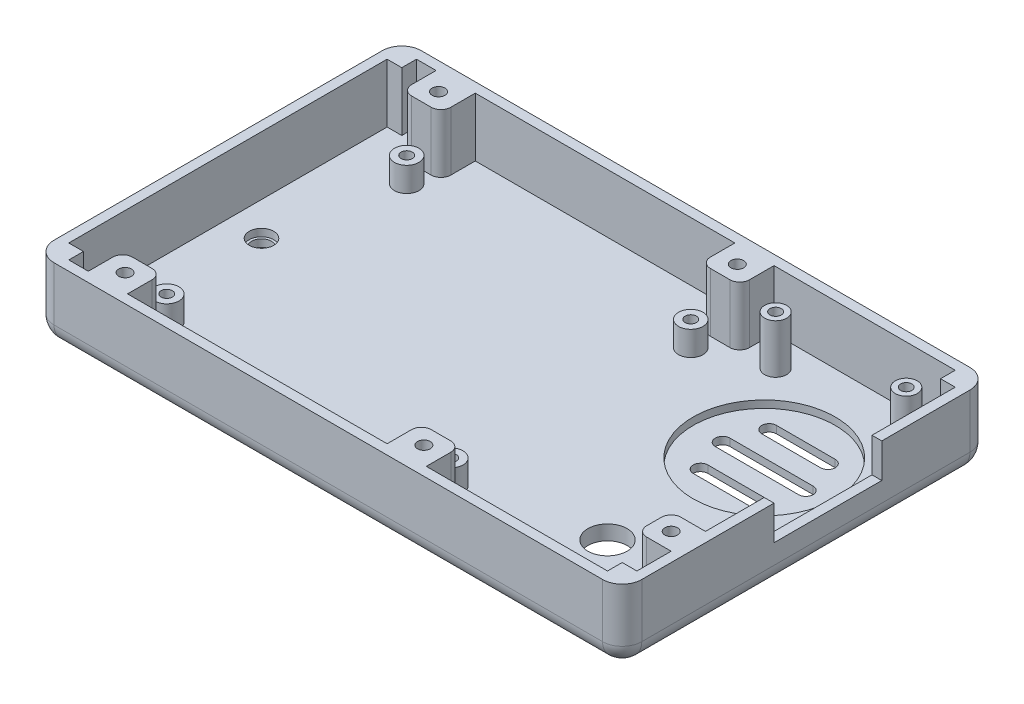
SolidWorks part; units mm, degrees
ref_plane "Front Plane" through (0, 0, 0) normal (0, 0, 1) x (1, 0, 0)
ref_plane "Top Plane" through (0, 0, 0) normal (0, 1, 0) x (1, 0, 0)
ref_plane "Right Plane" through (0, 0, 0) normal (1, 0, 0) x (0, 0, -1)
sketch "Sketch1" plane through (0, 0, 0) normal (0, 1, 0) x (1, 0, 0)
  line L1 (-60, 37.5) -> (60, 37.5)
  line L2 (-60, 37.5) -> (-60, -37.5)
  line L3 (-60, -37.5) -> (60, -37.5)
  line L4 (60, 37.5) -> (60, -37.5)
  line L5 (-60, 37.5) -> (60, -37.5) construction
  line L6 (-60, -37.5) -> (60, 37.5) construction
  point P0 (0, 0)
  dimension "D1" = 120
  dimension "D2" = 75
extrude "Main Structure" add sketch "Sketch1" along normal blind 15
sketch "Sketch2" plane through (0, 15, 0) normal (0, 1, 0) x (1, 0, 0)
  line L1 (-58, -35.5) -> (58, -35.5)
  line L2 (-58, -35.5) -> (-58, 35.5)
  line L3 (-58, 35.5) -> (58, 35.5)
  line L4 (58, -35.5) -> (58, 35.5)
  line L5 (-58, -35.5) -> (58, 35.5) construction
  line L6 (-58, 35.5) -> (58, -35.5) construction
  point P0 (0, 0)
  dimension "D1" = 71
  dimension "D2" = 116
extrude "Inside Cut" cut sketch "Sketch2" against normal blind 12
sketch "Sketch3" plane through (0, 3, 0) normal (0, 1, 0) x (1, 0, 0)
  line L0 (-58, 35.5) -> (-58, -35.5) construction
  line L1 (-58, -35.5) -> (58, -35.5) construction
  line L2 (58, 35.5) -> (-58, 35.5) construction
  circle A0 centre (-46, -24.5) radius 2.5
  circle A1 centre (-46, 24.5) radius 2.5
  circle A2 centre (-46, 24.5) radius 1.15
  circle A3 centre (-46, -24.5) radius 1.15
  circle A4 centre (12, 24.5) radius 2.5
  circle A5 centre (12, -24.5) radius 2.5
  circle A6 centre (12, 24.5) radius 1.15
  circle A7 centre (12, -24.5) radius 1.15
  dimension "D1" = 5
  dimension "D3" = 5
  dimension "D7" = 2.3
  dimension "D8" = 2.3
  dimension "D9" = 5
  dimension "D10" = 5
  dimension "D15" = 2.3
  dimension "D16" = 2.3
  dimension "D2" = 12
  dimension "D4" = 12
  dimension "D5" = 11
  dimension "D6" = 11
  dimension "D11" = 11
  dimension "D12" = 58
  dimension "D13" = 58
  dimension "D14" = 11
extrude "Pi Standoffs" add sketch "Sketch3" along normal blind 5
sketch "Sketch4" plane through (0, 3, 0) normal (0, 1, 0) x (1, 0, 0)
  line L0 (58, -35.5) -> (58, 35.5) construction
  line L1 (-58, -35.5) -> (58, -35.5) construction
  circle A0 centre (48, -30.5) radius 2
  circle A1 centre (48, -17.5) radius 2
  circle A2 centre (48, -17.5) radius 0.9
  circle A3 centre (48, -30.5) radius 0.9
  dimension "D1" = 4
  dimension "D4" = 4
  dimension "D6" = 1.8
  dimension "D7" = 1.8
  dimension "D2" = 10
  dimension "D3" = 5
  dimension "D5" = 13
extrude "Camera Standoffs" add sketch "Sketch4" along normal blind 5
fillet "Body Fillet 1" radius 4 1 edges at (-60, 0, 0)
fillet "Body Fillet 2" radius 4 3 edges at (-60, 9.5, -37.5) (-58.8284, 1.1716, -37.5) (2, 0, -37.5)
fillet "Body Fillet 3" radius 4 3 edges at (-60, 9.5, 37.5) (-58.8284, 1.1716, 37.5) (2, 0, 37.5)
fillet "Body Fillet 4" radius 4 5 edges at (60, 9.5, 37.5) (60, 1.1716, 36.3284) (60, 9.5, -37.5) (60, 1.1716, -36.3284) (60, 0, 0)
sketch "Sketch5" plane through (0, 3, 0) normal (0, 1, 0) x (1, 0, 0)
  line L0 (58, 35.5) -> (-58, 35.5) construction
  line L1 (58, -35.5) -> (58, 35.5) construction
  circle A0 centre (24.33, 29.5) radius 2.25
  circle A1 centre (51, 29.5) radius 2.25
  circle A2 centre (51, 29.5) radius 1.15
  circle A4 centre (24.33, 29.5) radius 1.15
  dimension "D1" = 4.5
  dimension "D3" = 4.5
  dimension "D6" = 2.3
  dimension "D7" = 2.3
  dimension "D2" = 6
  dimension "D4" = 7
  dimension "D5" = 26.67
extrude "Fona Standoffs" add sketch "Sketch5" along normal blind 10
sketch "Sketch6" plane through (0, 3, 0) normal (0, 1, 0) x (1, 0, 0)
  line L1 (-58, -35.5) -> (-55, -35.5)
  line L2 (-58, -35.5) -> (-58, -32.5)
  line L3 (-58, -32.5) -> (-55, -32.5)
  line L4 (-55, -35.5) -> (-55, -32.5)
  line L5 (-58, 35.5) -> (-55, 35.5)
  line L6 (-58, 35.5) -> (-58, 32.5)
  line L7 (-58, 32.5) -> (-55, 32.5)
  line L8 (-55, 35.5) -> (-55, 32.5)
  line L9 (58, -35.5) -> (55, -35.5)
  line L10 (58, -35.5) -> (58, -32.5)
  line L11 (58, -32.5) -> (55, -32.5)
  line L12 (55, -35.5) -> (55, -32.5)
  line L13 (58, 35.5) -> (55, 35.5)
  line L14 (58, 35.5) -> (58, 32.5)
  line L15 (58, 32.5) -> (55, 32.5)
  line L16 (55, 35.5) -> (55, 32.5)
  dimension "D1" = 3
  dimension "D2" = 3
  dimension "D3" = 3
  dimension "D4" = 3
  dimension "D5" = 3
  dimension "D6" = 3
  dimension "D7" = 3
  dimension "D8" = 3
extrude "Corner Support" add sketch "Sketch6" along normal blind 12
sketch "Sketch8" plane through (60, 0, 0) normal (1, 0, 0) x (0, 0, -1)
  line L0 (-33.5, 15) -> (-33.5, 4) construction
  line L1 (-6.5, 15) -> (15.5, 15)
  line L2 (-6.5, 15) -> (-6.5, 8)
  line L3 (-6.5, 8) -> (15.5, 8)
  line L4 (15.5, 15) -> (15.5, 8)
  line L5 (-6.5, 15) -> (15.5, 8) construction
  line L6 (-6.5, 8) -> (15.5, 15) construction
  line L7 (-33.5, 4) -> (33.5, 4) construction
  line L8 (-33.5, 15) -> (33.5, 15) construction
  point P0 (4.5, 11.5)
  dimension "D1" = 27
  dimension "D2" = 4
  dimension "D3" = 0
  dimension "D4" = 22
extrude "Charger Cutout" cut sketch "Sketch8" against normal blind 10
sketch "Sketch9" plane through (0, 3, 0) normal (0, 1, 0) x (1, 0, 0)
  line L1 (-51, -28.5) -> (-43, -28.5)
  line L2 (-51, -28.5) -> (-51, -35.5)
  line L3 (-51, -35.5) -> (-43, -35.5)
  line L4 (-43, -28.5) -> (-43, -35.5)
  line L5 (-51, -28.5) -> (-43, -35.5) construction
  line L6 (-51, -35.5) -> (-43, -28.5) construction
  line L7 (-55, -35.5) -> (55, -35.5) construction
  line L8 (51, -18.5) -> (58, -18.5)
  line L9 (-51, 35.5) -> (-43, 35.5)
  line L10 (-51, 35.5) -> (-51, 28.5)
  line L11 (-51, 28.5) -> (-43, 28.5)
  line L12 (-43, 35.5) -> (-43, 28.5)
  line L13 (-51, 35.5) -> (-43, 28.5) construction
  line L14 (-51, 28.5) -> (-43, 35.5) construction
  line L15 (55, 35.5) -> (-55, 35.5) construction
  line L16 (-58, 32.5) -> (-58, -32.5) construction
  line L17 (58, -32.5) -> (58, 32.5) construction
  line L18 (10, 35.5) -> (18, 35.5)
  line L19 (10, 35.5) -> (10, 28.5)
  line L20 (10, 28.5) -> (18, 28.5)
  line L21 (18, 35.5) -> (18, 28.5)
  line L22 (10, 35.5) -> (18, 28.5) construction
  line L23 (10, 28.5) -> (18, 35.5) construction
  line L24 (51, -18.5) -> (51, -25.5)
  line L25 (10, -28.5) -> (18, -28.5)
  line L26 (10, -28.5) -> (10, -35.5)
  line L27 (10, -35.5) -> (18, -35.5)
  line L28 (18, -28.5) -> (18, -35.5)
  line L29 (10, -28.5) -> (18, -35.5) construction
  line L30 (10, -35.5) -> (18, -28.5) construction
  line L31 (51, -25.5) -> (58, -25.5)
  line L32 (58, -18.5) -> (58, -25.5)
  line L33 (51, -18.5) -> (58, -25.5) construction
  line L34 (51, -25.5) -> (58, -18.5) construction
  point P0 (-47, -32)
  point P9 (54.5, -22)
  point P11 (-47, 32)
  point P16 (14, 32)
  point P29 (14, -32)
  dimension "D5" = 0
  dimension "D10" = 7
  dimension "D16" = 10
  dimension "D2" = 0
  dimension "D3" = 7
  dimension "D4" = 8
  dimension "D6" = 8
  dimension "D7" = 7
  dimension "D8" = 7
  dimension "D9" = 0
  dimension "D11" = 7
  dimension "D12" = 7
  dimension "D13" = 8
  dimension "D14" = 0
  dimension "D15" = 40
  dimension "D17" = 8
  dimension "D18" = 7
  dimension "D19" = 40
  dimension "D20" = 0
extrude "Mounting Structure" add sketch "Sketch9" along normal blind 12
fillet "Mounting Structure Fillet" radius 2 10 edges at (-43, 9, -28.5) (-51, 9, -28.5) (10, 9, -28.5) (18, 9, -28.5) (10, 9, 28.5) (18, 9, 28.5) (-51, 9, 28.5) (-43, 9, 28.5) (51, 9, 18.5) (51, 9, 25.5)
sketch "Sketch10" plane through (0, 15, 0) normal (0, 1, 0) x (1, 0, 0)
  line L0 (-51, 35.5) -> (-51, 30.5) construction
  line L1 (-49, 28.5) -> (-45, 28.5) construction
  line L2 (-51, -30.5) -> (-51, -35.5) construction
  line L3 (-45, -28.5) -> (-49, -28.5) construction
  line L4 (10, -30.5) -> (10, -35.5) construction
  line L5 (16, -28.5) -> (12, -28.5) construction
  line L6 (12, 28.5) -> (16, 28.5) construction
  line L7 (10, 35.5) -> (10, 30.5) construction
  line L8 (51, -20.5) -> (51, -23.5) construction
  line L9 (53, -25.5) -> (58, -25.5) construction
  circle A0 centre (-47, 32) radius 1.3
  circle A1 centre (-47, -32) radius 1.3
  circle A2 centre (14, -32) radius 1.3
  circle A3 centre (14, 32) radius 1.3
  circle A4 centre (54.5, -22) radius 1.3
  point P10 (-47, -28.5)
  dimension "D1" = 2.6
  dimension "D4" = 2.6
  dimension "D7" = 2.6
  dimension "D10" = 2.6
  dimension "D13" = 2.6
  dimension "D2" = 4
  dimension "D3" = 3.5
  dimension "D5" = 4
  dimension "D6" = 3.5
  dimension "D8" = 4
  dimension "D9" = 3.5
  dimension "D11" = 3.5
  dimension "D12" = 4
  dimension "D14" = 3.5
  dimension "D15" = 3.5
extrude "Case Mounting Holes" cut sketch "Sketch10" against normal blind 15
sketch "Sketch13" plane through (0, 0, 0) normal (0, -1, 0) x (1, 0, 0)
  circle A0 centre (-47, 32) radius 2.9
  circle A1 centre (14, 32) radius 2.9
  circle A2 centre (14, -32) radius 2.9
  circle A3 centre (-47, -32) radius 2.9
  circle A4 centre (54.5, 22) radius 2.9
  dimension "D1" = 5.8
  dimension "D2" = 5.8
  dimension "D3" = 5.8
  dimension "D4" = 5.8
  dimension "D5" = 5.8
extrude "Case Screw Head Holes" cut sketch "Sketch13" against normal blind 8.85
sketch "Sketch14" plane through (0, 3, 0) normal (0, 1, 0) x (1, 0, 0)
  line L0 (55, 35.5) -> (18, 35.5) construction
  line L1 (58, -32.5) -> (58, -25.5) construction
  circle A0 centre (39, 12.5) radius 14.5
  dimension "D1" = 29
  dimension "D2" = 23
  dimension "D3" = 19
extrude "Speaker Holder" cut sketch "Sketch14" against normal blind 1.5
sketch "Sketch23" plane through (0, 1.5, 0) normal (0, 1, 0) x (1, 0, 0)
  line L0 (33, 19.5) -> (45, 19.5) construction
  line L1 (33, 21) -> (45, 21)
  line L2 (33, 18) -> (45, 18)
  line L3 (30.5, 12.5) -> (47.5, 12.5) construction
  line L4 (30.5, 14) -> (47.5, 14)
  line L5 (30.5, 11) -> (47.5, 11)
  line L6 (33, 5.5) -> (45, 5.5) construction
  line L7 (33, 7) -> (45, 7)
  line L8 (33, 4) -> (45, 4)
  arc A0 (33, 21) -> (33, 18) centre (33, 19.5) ccw
  arc A1 (45, 18) -> (45, 21) centre (45, 19.5) ccw
  circle A2 centre (39, 12.5) radius 14.5 construction
  arc A3 (30.5, 14) -> (30.5, 11) centre (30.5, 12.5) ccw
  arc A4 (47.5, 11) -> (47.5, 14) centre (47.5, 12.5) ccw
  arc A5 (33, 7) -> (33, 4) centre (33, 5.5) ccw
  arc A6 (45, 4) -> (45, 7) centre (45, 5.5) ccw
  point P2 (39, 19.5)
  point P11 (39, 12.5)
  point P19 (39, 5.5)
  dimension "D3" = 7
  dimension "D1" = 3
  dimension "D2" = 15
  dimension "D4" = 3
  dimension "D5" = 20
  dimension "D6" = 3
  dimension "D7" = 15
  dimension "D8" = 7
extrude "Sound Cutout" cut sketch "Sketch23" against normal blind 1.5
sketch "Sketch25" plane through (0, 3, 0) normal (0, 1, 0) x (1, 0, 0)
  circle A0 centre (-51.1477, 0) radius 2.5
  dimension "D1" = 5
extrude "Microphone holder" cut sketch "Sketch25" against normal blind 1.5
sketch "Sketch26" plane through (0, 1.5, 0) normal (0, 1, 0) x (1, 0, 0)
  circle A0 centre (-51.1477, 0) radius 2
  dimension "D1" = 4
extrude "Microphone Cutout" cut sketch "Sketch26" against normal blind 1.5
sketch "Sketch27" plane through (0, 3, 0) normal (0, 1, 0) x (1, 0, 0)
  line L0 (-58, 32.5) -> (-58, -32.5) construction
  line L1 (55, 35.5) -> (18, 35.5) construction
  circle A0 centre (37.5, -18) radius 4
  dimension "D1" = 8
  dimension "D2" = 95.5
  dimension "D3" = 53.5
extrude "Camera Cutout" cut sketch "Sketch27" against normal blind 10
